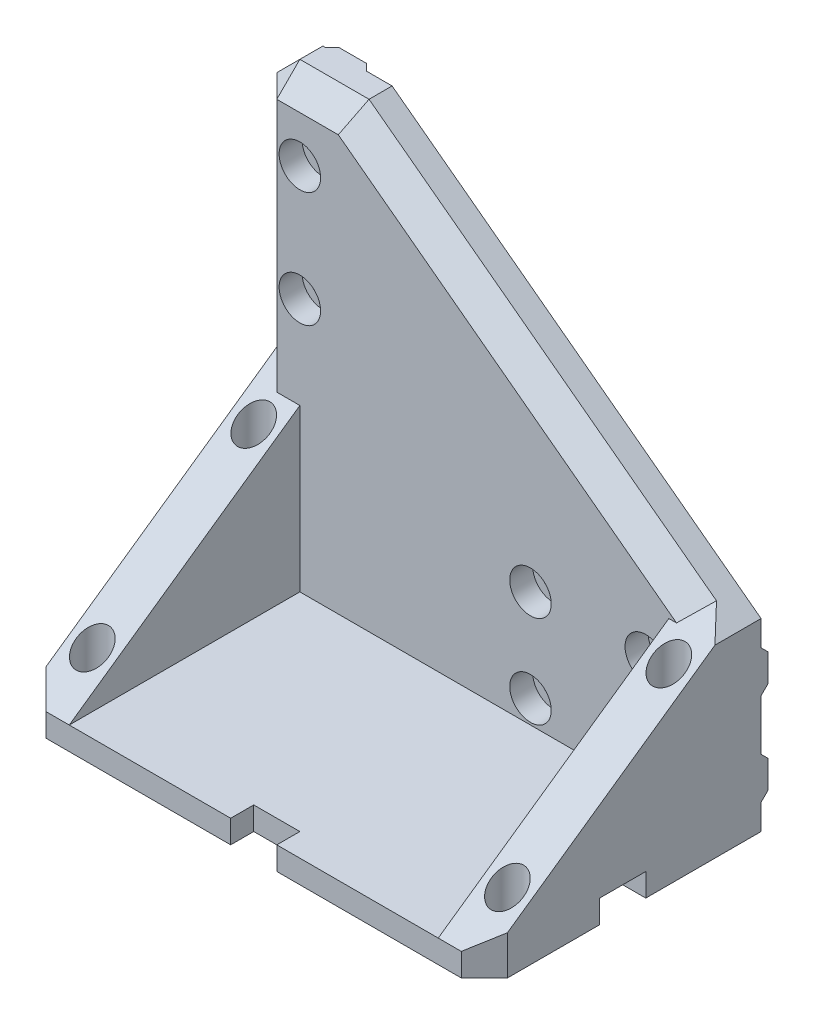
SolidWorks part; units mm, degrees
ref_plane "Płaszczyzna przednia" through (0, 0, 0) normal (0, 0, 1) x (1, 0, 0)
ref_plane "Płaszczyzna górna" through (0, 0, 0) normal (0, 1, 0) x (1, 0, 0)
ref_plane "Płaszczyzna prawa" through (0, 0, 0) normal (1, 0, 0) x (0, 0, -1)
sketch "Sketch1" plane through (0, 0, 0) normal (0, 0, 1) x (1, 0, 0)
  line L0 (0, 0) -> (100, 0)
  line L1 (100, 0) -> (100, 40)
  line L2 (100, 40) -> (20, 100)
  line L3 (20, 100) -> (0, 100)
  line L4 (0, 100) -> (0, 0)
  line L5 (10, 100) -> (10, 0) construction
  line L6 (30, 100) -> (30, 0) construction
  line L8 (100, 30) -> (0, 30) construction
  dimension "D1" = 20
  dimension "D2" = 40
  dimension "D3" = 100
extrude "Boss-Extrude1" add sketch "Sketch1" along normal blind 10
sketch "Sketch2" plane through (0, 0, 0) normal (0, 0, 1) x (1, 0, 0)
  line L5 (10, 100) -> (10, 0) construction
  line L7 (100, 10) -> (0, 10) construction
  line L8 (100, 30) -> (0, 30) construction
  line L9 (0, 0) -> (100, 0) construction
  line L10 (0, 100) -> (0, 0) construction
  line L11 (100, 0) -> (100, 40) construction
  line L12 (0, 100) -> (0, 0) construction
  line L13 (20, 100) -> (0, 100) construction
  line L14 (0, 0) -> (100, 0) construction
  circle A0 centre (10, 85) radius 2.6
  circle A2 centre (10, 60) radius 2.6
  circle A4 centre (85, 30) radius 2.6
  circle A5 centre (85, 10) radius 2.6
  circle A6 centre (60, 10) radius 2.6
  circle A7 centre (60, 30) radius 2.6
  dimension "D9" = 60
  dimension "D1" = 10
  dimension "D2" = 10
  dimension "D4" = 15
  dimension "D6" = 60
  dimension "D7" = 15
  dimension "D8" = 20
extrude "Cut-Extrude1" cut sketch "Sketch2" along normal through all
sketch "Sketch3" plane through (0, 0, 0) normal (0, 0, 1) x (1, 0, 0)
  line L0 (0, 100) -> (0, 0) construction
  line L1 (100, 0) -> (100, 40) construction
  line L2 (100, 25.5) -> (40, 25.5)
  line L3 (100, 25.5) -> (100, 34.5)
  line L4 (100, 34.5) -> (40, 34.5)
  line L5 (40, 25.5) -> (40, 34.5)
  line L6 (20, 100) -> (0, 100) construction
  line L7 (100, 5.5) -> (40, 5.5)
  line L8 (100, 5.5) -> (100, 14.5)
  line L9 (100, 14.5) -> (40, 14.5)
  line L10 (40, 5.5) -> (40, 14.5)
  line L11 (14.5, 100) -> (5.5, 100)
  line L12 (14.5, 100) -> (14.5, 40)
  line L13 (14.5, 40) -> (5.5, 40)
  line L14 (5.5, 100) -> (5.5, 40)
  line L15 (0, 0) -> (100, 0) construction
  circle A0 centre (60, 30) radius 2.6 construction
  circle A1 centre (60, 10) radius 2.6 construction
  circle A3 centre (10, 60) radius 2.6 construction
  dimension "D3" = 4.5
  dimension "D6" = 4.5
  dimension "D10" = 4.5
  dimension "D1" = 40
  dimension "D2" = 40
  dimension "D4" = 9
  dimension "D5" = 9
  dimension "D8" = 9
  dimension "D11" = 40
extrude "Boss-Extrude3" add sketch "Sketch3" against normal blind 1.46 from surface starting at face at (12.6, 85, 0)
extrude "Cut-Extrude2" cut sketch "Sketch2<2>" along normal through all both and the other way through all
sketch "Sketch2<2>" plane through (0, 0, 0) normal (0, 0, 1) x (1, 0, 0) same geometry as "Sketch2"
chamfer "Chamfer1" distance 1.46 angle 45 6 edges at (14.5, 70, -1.46) (5.5, 70, -1.46) (70, 5.5, -1.46) (70, 14.5, -1.46) (70, 25.5, -1.46) (70, 34.5, -1.46)
sketch "Sketch4" plane through (0, 0, 0) normal (0, 0, 1) x (1, 0, 0)
  circle A0 centre (10, 85) radius 4.5
  circle A3 centre (10, 60) radius 4.5
  circle A4 centre (60, 30) radius 4.5
  circle A5 centre (85, 30) radius 4.5
  circle A6 centre (85, 10) radius 4.5
  circle A7 centre (60, 10) radius 4.5
  dimension "D1" = 9
extrude "Cut-Extrude3" cut sketch "Sketch4" against normal blind 5 from surface starting at face at (12.6, 85, 10)
sketch "Sketch5" plane through (0, 0, 0) normal (0, 1, 0) x (1, 0, 0)
  line L0 (100, -35) -> (0, -35) construction
  line L1 (100, -60) -> (0, -60)
  line L2 (100, -60) -> (100, -10)
  line L3 (100, -10) -> (0, -10)
  line L4 (0, -60) -> (0, -10)
  line L14 (0, -10) -> (100, -10) construction
  dimension "D1" = 50
extrude "Boss-Extrude4" add sketch "Sketch5" along normal blind 5
sketch "Sketch8" plane through (0, 0, 0) normal (1, 0, 0) x (0, 0, -1)
  line L0 (-10, 5) -> (-60, 5)
  line L1 (-60, 5) -> (-10, 40)
  line L2 (-10, 40) -> (-10, 5)
  line L3 (-10, 5) -> (-10, 40) construction
  line L4 (-10, 100) -> (-10, 5) construction
extrude "Boss-Extrude5" add sketch "Sketch8" along normal blind 10
extrude "Boss-Extrude6" add sketch "Sketch8<2>" against normal blind 10 from surface starting at face at (100, 17.8571, 9.5829)
sketch "Sketch8<2>" plane through (0, 0, 0) normal (1, 0, 0) x (0, 0, -1) same geometry as "Sketch8"
sketch "Sketch10" plane through (0, 0, 0) normal (0, 1, 0) x (1, 0, 0)
  line L0 (0, -60) -> (0, 0) construction
  line L1 (95, -50) -> (5, -50) construction
  line L2 (95, -50) -> (95, -15) construction
  line L3 (95, -15) -> (5, -15) construction
  line L4 (5, -50) -> (5, -15) construction
  line L5 (95, -50) -> (5, -15) construction
  line L6 (95, -15) -> (5, -50) construction
  line L7 (100, -60) -> (100, 0) construction
  line L8 (0, -60) -> (100, -60) construction
  line L9 (0, 0) -> (100, 0) construction
  circle A0 centre (5, -50) radius 1.75
  circle A1 centre (95, -50) radius 1.75
  circle A2 centre (95, -15) radius 1.75
  circle A3 centre (5, -15) radius 1.75
  point P0 (50, -32.5)
  dimension "D5" = 3.5
  dimension "D1" = 5
  dimension "D2" = 5
  dimension "D3" = 10
  dimension "D4" = 15
extrude "Cut-Extrude4" cut sketch "Sketch10" along normal through all both and the other way through all
sketch "Sketch11" plane through (0, 0, 0) normal (0, 1, 0) x (1, 0, 0)
  circle A0 centre (5, -15) radius 3.5
  circle A1 centre (5, -50) radius 3.5
  circle A2 centre (95, -50) radius 3.5
  circle A3 centre (95, -15) radius 3.5
  dimension "D1" = 7
extrude "Cut-Extrude5" cut sketch "Sketch11" against normal up to surface (-5 mm away) from surface up to face at (50, 5, 35) starting at face at (10, 100, 2.135)
sketch "Sketch12" plane through (0, 0, 0) normal (0, 1, 0) x (1, 0, 0)
  line L0 (55, -60) -> (45, -60)
  line L1 (55, -60) -> (55, -55)
  line L2 (45, -60) -> (45, -55)
  line L3 (55, -55) -> (45, -55)
  line L4 (0, -60) -> (100, -60) construction
  line L5 (100, -60) -> (100, 0) construction
  line L6 (100, -35) -> (100, -25)
  line L7 (100, -35) -> (95, -35)
  line L8 (100, -25) -> (95, -25)
  line L9 (95, -35) -> (95, -25)
  line L10 (0, -35) -> (0, -25)
  line L11 (0, -35) -> (5, -35)
  line L12 (0, -25) -> (5, -25)
  line L13 (5, -35) -> (5, -25)
  line L14 (0, -60) -> (0, 0) construction
  dimension "D1" = 5
  dimension "D2" = 10
  dimension "D3" = 45
  dimension "D4" = 10
  dimension "D5" = 5
  dimension "D6" = 25
  dimension "D7" = 10
  dimension "D8" = 5
  dimension "D9" = 25
extrude "Cut-Extrude6" cut sketch "Sketch12" along normal blind 5
chamfer "Chamfer2" distance 5 angle 45 6 edges at (100, 2.5, 60) (0, 2.5, 60) (0, 100, 5) (0, 70, 10) (10, 100, 10) (60, 70, 10)
